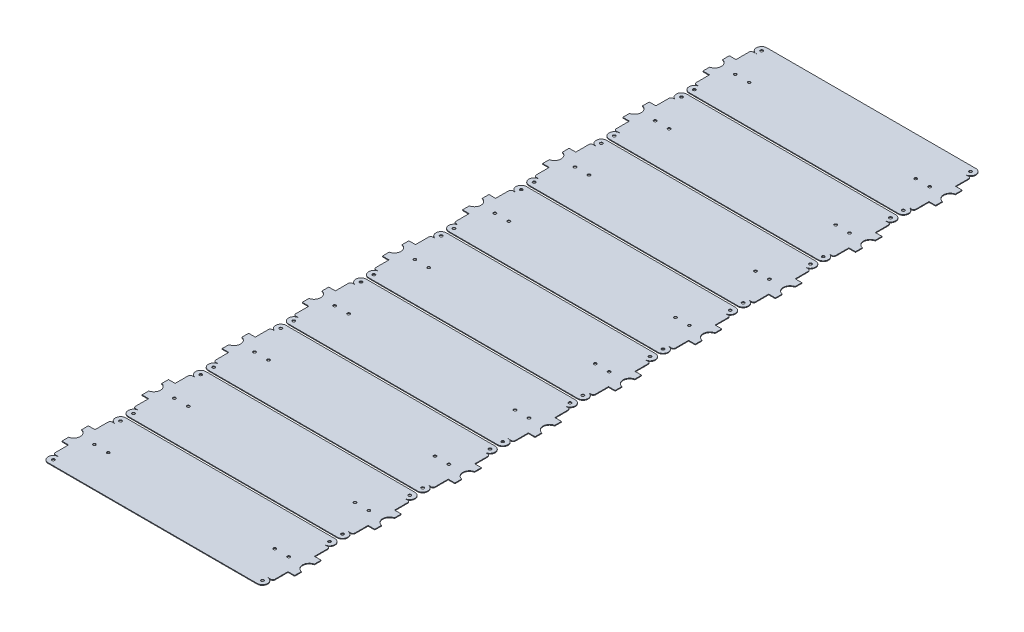
SolidWorks part; units mm, degrees
ref_plane "Front Plane" through (0, 0, 0) normal (0, 0, 1) x (1, 0, 0)
ref_plane "Top Plane" through (0, 0, 0) normal (0, 1, 0) x (1, 0, 0)
ref_plane "Right Plane" through (0, 0, 0) normal (1, 0, 0) x (0, 0, -1)
sketch "Sketch1" plane through (0, 0, 0) normal (0, 1, 0) x (1, 0, 0)
  line L1 (-157.5, 40.75) -> (157.5, 40.75) construction
  line L2 (-157.5, 40.75) -> (-157.5, -40.75) construction
  line L3 (-157.5, -40.75) -> (157.5, -40.75) construction
  line L4 (157.5, 40.75) -> (157.5, -40.75) construction
  line L5 (-157.5, 40.75) -> (157.5, -40.75) construction
  line L6 (-157.5, -40.75) -> (157.5, 40.75) construction
  line L19 (154.5, -37.75) -> (-154.5, -37.75) construction
  line L20 (154.5, -37.75) -> (154.5, 37.75) construction
  line L21 (154.5, 37.75) -> (-154.5, 37.75) construction
  line L22 (-154.5, -37.75) -> (-154.5, 37.75) construction
  line L23 (154.5, -37.75) -> (-154.5, 37.75) construction
  line L24 (154.5, 37.75) -> (-154.5, -37.75) construction
  line L25 (150, 55.75) -> (-150, 55.75)
  line L28 (-167.025, 19) -> (-167.025, 9.3127)
  line L31 (-150, -55.75) -> (150, -55.75)
  line L34 (167.025, -19) -> (167.025, -9.3127)
  line L36 (-157.5, 0) -> (-167.025, 0) construction
  line L37 (157.5, 0) -> (167.025, 0) construction
  line L38 (-157.5, 37.75) -> (-154.5, 37.75) construction
  line L43 (-167.025, 0) -> (-169.025, 0) construction
  line L44 (-167.025, -9.3127) -> (-167.025, -19)
  line L45 (-154.5, 37.75) -> (-154.5, 40.75) construction
  line L46 (-154.5, -40.75) -> (-154.5, -37.75) construction
  line L47 (-154.5, -37.75) -> (-157.5, -37.75) construction
  line L48 (154.5, -40.75) -> (154.5, -37.75) construction
  line L49 (154.5, -37.75) -> (157.5, -37.75) construction
  line L50 (154.5, 37.75) -> (154.5, 40.75) construction
  line L51 (157.5, 37.75) -> (154.5, 37.75) construction
  line L53 (-159, 40.75) -> (-154.5, 40.75)
  line L54 (-167.025, 19) -> (-157.5, 19)
  line L55 (-157.5, 19) -> (-157.5, 37.75)
  line L56 (-167.025, -19) -> (-157.5, -19)
  line L57 (-157.5, -19) -> (-157.5, -37.75)
  line L62 (167.025, -19) -> (157.5, -19)
  line L63 (157.5, -19) -> (157.5, -37.75)
  line L64 (167.025, 19) -> (157.5, 19)
  line L65 (157.5, 19) -> (157.5, 37.75)
  line L67 (159, 40.75) -> (154.5, 40.75)
  line L68 (0, 48.25) -> (0, 0) construction
  line L69 (150, 0) -> (0, 0) construction
  line L70 (-167.025, 9.3127) -> (-167.025, 0) construction
  line L71 (-150, 48.25) -> (150, 48.25) construction
  line L72 (-150, 48.25) -> (-150, -48.25) construction
  line L73 (-150, -48.25) -> (150, -48.25) construction
  line L74 (150, 48.25) -> (150, -48.25) construction
  line L75 (-167.025, 0) -> (-167.025, -9.3127) construction
  line L76 (169.025, 0) -> (167.025, 0) construction
  line L77 (167.025, 9.3127) -> (167.025, 19)
  line L78 (167.025, 9.3127) -> (167.025, 0) construction
  line L79 (167.025, 0) -> (167.025, -9.3127) construction
  line L80 (-150, 55.75) -> (-150, 40.75) construction
  line L81 (150, 55.75) -> (150, 40.75) construction
  line L82 (-150, -55.75) -> (-150, -40.75) construction
  line L83 (150, -55.75) -> (150, -40.75) construction
  line L84 (-154.5, -40.75) -> (-150, -40.75)
  line L85 (-154.5, 40.75) -> (-150, 40.75)
  line L86 (150, 40.75) -> (154.5, 40.75)
  line L87 (150, -40.75) -> (154.5, -40.75)
  line L88 (-157.5, -48.25) -> (-157.5, -37.75) construction
  line L89 (-159.5, 0) -> (0, 0) construction
  arc A0 (-154.5, 40.75) -> (-157.5, 37.75) centre (-154.5, 37.75) ccw
  arc A1 (-157.5, -37.75) -> (-154.5, -40.75) centre (-154.5, -37.75) ccw
  arc A2 (154.5, -40.75) -> (157.5, -37.75) centre (154.5, -37.75) ccw
  arc A3 (154.5, 40.75) -> (157.5, 37.75) centre (154.5, 37.75) cw
  circle A8 centre (-150, 48.25) radius 2
  circle A9 centre (150, 48.25) radius 2
  circle A10 centre (150, -48.25) radius 2
  circle A11 centre (-150, -48.25) radius 2
  circle A12 centre (-169.025, 0) radius 9.525 construction
  arc A13 (-167.025, -9.3127) -> (-167.025, 9.3127) centre (-169.025, 0) ccw
  circle A14 centre (169.025, 0) radius 9.525 construction
  arc A15 (167.025, 9.3127) -> (167.025, -9.3127) centre (169.025, 0) ccw
  arc A16 (150, 40.75) -> (150, 55.75) centre (150, 48.25) ccw
  arc A17 (-150, 55.75) -> (-150, 40.75) centre (-150, 48.25) ccw
  arc A18 (-150, -40.75) -> (-150, -55.75) centre (-150, -48.25) ccw
  arc A19 (150, -40.75) -> (150, -55.75) centre (150, -48.25) cw
  circle A20 centre (139.5, 0) radius 2
  circle A21 centre (119.5, 0) radius 2
  circle A22 centre (-139.5, 0) radius 2
  circle A23 centre (-119.5, 0) radius 2
  point P0 (0, 0)
  point P5 (0, 0)
  point P31 (0, 0)
  point P45 (-159.5, 0)
  point P50 (159.5, 0)
  dimension "D5" = 38
  dimension "D9" = 19.05
  dimension "D11" = 20
  dimension "D16" = 2
  dimension "D13" = 4
  dimension "D18" = 19.05
  dimension "D6" = 4
  dimension "D14" = 4
  dimension "D1" = 81.5
  dimension "D2" = 300
  dimension "D3" = 20
  dimension "D4" = 3
  dimension "D7" = 38
  dimension "D8" = 2
  dimension "D10" = 15
  dimension "D12" = 2
  dimension "D15" = 20
  dimension "D17" = 2
  dimension "D19" = 20
extrude "Boss-Extrude1" add sketch "Sketch1" along normal blind 1 contours A15 L77 L64 L65 A3 L67 L25 L53 A0 L55 L54 L28 A13 L44 L56 L57 A1 L31 A2 L63 L62 L34 A11 A10 A9 A8 region at (0, 0, 0)
pattern_linear "LPattern1" count 9 spacing 115 along (0, 0, -1) of bodies 101
